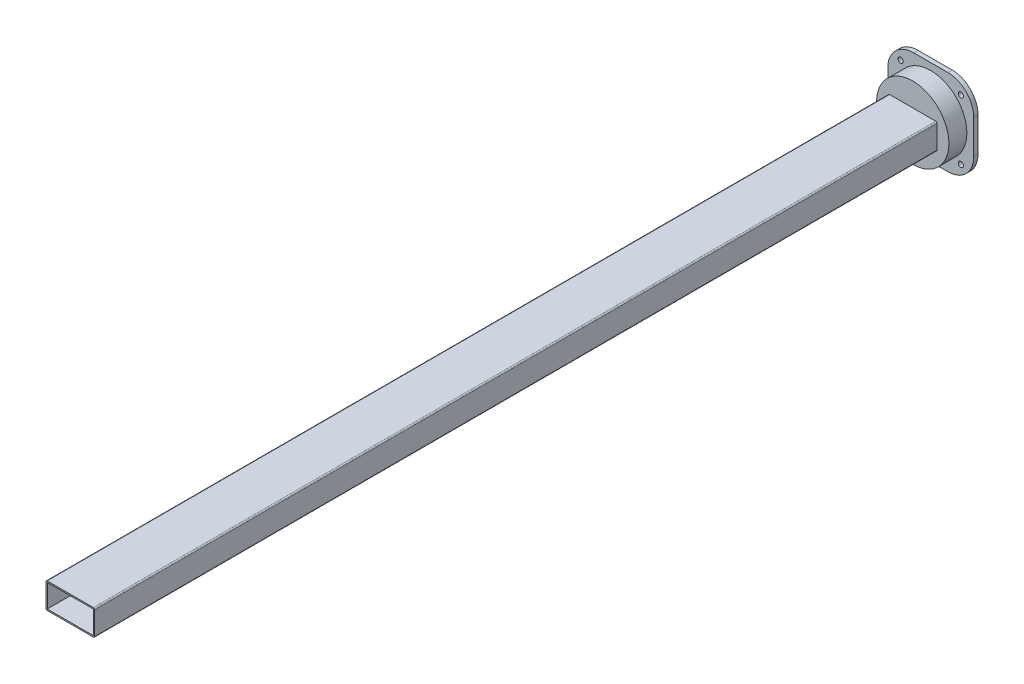
SolidWorks part; units mm, degrees
ref_plane "Спереди" through (0, 0, 0) normal (0, 0, 1) x (1, 0, 0)
ref_plane "Сверху" through (0, 0, 0) normal (0, 1, 0) x (1, 0, 0)
ref_plane "Справа" through (0, 0, 0) normal (1, 0, 0) x (0, 0, -1)
sketch "Эскиз2" plane through (0, 0, 0) normal (0, 0, 1) x (1, 0, 0)
  line L1 (-26.767, 13.3835) -> (26.767, 13.3835)
  line L2 (-26.767, 13.3835) -> (-26.767, -13.3835)
  line L3 (-26.767, -13.3835) -> (26.767, -13.3835)
  line L4 (26.767, 13.3835) -> (26.767, -13.3835)
  line L5 (-26.767, 13.3835) -> (26.767, -13.3835) construction
  line L6 (-26.767, -13.3835) -> (26.767, 13.3835) construction
  line L7 (-26.767, 14.8835) -> (26.767, 14.8835)
  line L8 (-28.267, 13.3835) -> (-28.267, -13.3835)
  line L9 (-26.767, -14.8835) -> (26.767, -14.8835)
  line L10 (28.267, 13.3835) -> (28.267, -13.3835)
  line L11 (-28.267, 14.8835) -> (28.267, -14.8835) construction
  line L12 (-28.267, -14.8835) -> (28.267, 14.8835) construction
  arc A0 (-26.767, 14.8835) -> (-28.267, 13.3835) centre (-26.767, 13.3835) ccw
  arc A1 (-26.767, -14.8835) -> (-28.267, -13.3835) centre (-26.767, -13.3835) cw
  arc A2 (28.267, -13.3835) -> (26.767, -14.8835) centre (26.767, -13.3835) cw
  arc A3 (26.767, 14.8835) -> (28.267, 13.3835) centre (26.767, 13.3835) cw
  point P0 (0, 0)
  point P6 (0, 0)
extrude "Бобышка-Вытянуть1" add sketch "Эскиз2" along normal blind 1000
sketch "Эскиз6" plane through (0, 0, 0) normal (0, 0, -1) x (-1, 0, 0)
  line L1 (-19.93, 49.9553) -> (19.93, 49.9553)
  line L2 (-49.93, 19.9553) -> (-49.93, -19.9553)
  line L3 (-19.93, -49.9553) -> (19.93, -49.9553)
  line L4 (49.93, 19.9553) -> (49.93, -19.9553)
  line L5 (-49.93, 49.9553) -> (49.93, -49.9553) construction
  line L6 (-49.93, -49.9553) -> (49.93, 49.9553) construction
  line L11 (-45.0384, 45.0661) -> (45.0384, -45.0661) construction
  line L12 (-45.0384, -45.0661) -> (45.0384, 45.0661) construction
  arc A1 (-49.93, 19.9553) -> (-19.93, 49.9553) centre (-19.93, 19.9553) cw
  arc A2 (19.93, -49.9553) -> (49.93, -19.9553) centre (19.93, -19.9553) ccw
  arc A3 (-19.93, -49.9553) -> (-49.93, -19.9553) centre (-19.93, -19.9553) cw
  arc A4 (49.93, 19.9553) -> (19.93, 49.9553) centre (19.93, 19.9553) ccw
  point P0 (0, 0)
  point P7 (0, 0)
  dimension "D1" = 30
  dimension "D2" = 30
extrude "Бобышка-Вытянуть2" add sketch "Эскиз6" along normal blind 5
sketch "Эскиз8" plane through (0, 0, 1000) normal (0, 0, 1) x (1, 0, 0)
  line L1 (-26.767, 13.3835) -> (26.767, 13.3835)
  line L2 (-26.767, 13.3835) -> (-26.767, -13.3835)
  line L3 (-26.767, -13.3835) -> (26.767, -13.3835)
  line L4 (26.767, 13.3835) -> (26.767, -13.3835)
  line L5 (-26.767, 13.3835) -> (26.767, -13.3835) construction
  line L6 (-26.767, -13.3835) -> (26.767, 13.3835) construction
  point P0 (0, 0)
extrude "Вырез-Вытянуть2" cut sketch "Эскиз8" against normal blind 1010
sketch "Эскиз9" plane through (0, 0, -5) normal (0, 0, -1) x (-1, 0, 0)
  circle A0 centre (0, 0) radius 35
  circle A1 centre (0, 0) radius 40
extrude "Вырез-Вытянуть4" cut sketch "Эскиз9" against normal blind 1010
sketch "Эскиз10" plane through (0, 0, -5) normal (0, 0, -1) x (-1, 0, 0)
  circle A1 centre (-35, 35) radius 3
  circle A2 centre (-35, -35) radius 3
  circle A3 centre (35, -35) radius 3
  circle A4 centre (35, 35) radius 3
  point P0 (0, 0)
extrude "Вырез-Вытянуть7" cut sketch "Эскиз10" against normal blind 1010
sketch "Эскиз11" plane through (0, 0, -5) normal (0, 0, -1) x (-1, 0, 0)
  circle A0 centre (0, 0) radius 32
  circle A1 centre (0, 0) radius 42
extrude "Бобышка-Вытянуть3" add sketch "Эскиз11" against normal blind 25.9413 contours A1
extrude "Вырез-Вытянуть8" cut sketch "Эскиз9<2>" against normal blind 23.9413
sketch "Эскиз9<2>" plane through (0, 0, -5) normal (0, 0, -1) x (-1, 0, 0) same geometry as "Эскиз9"
extrude "Вырез-Вытянуть9" cut sketch "Эскиз8<2>" against normal blind 2000 and the other way blind 23.9413
sketch "Эскиз8<2>" plane through (0, 0, 1000) normal (0, 0, 1) x (1, 0, 0) same geometry as "Эскиз8"
